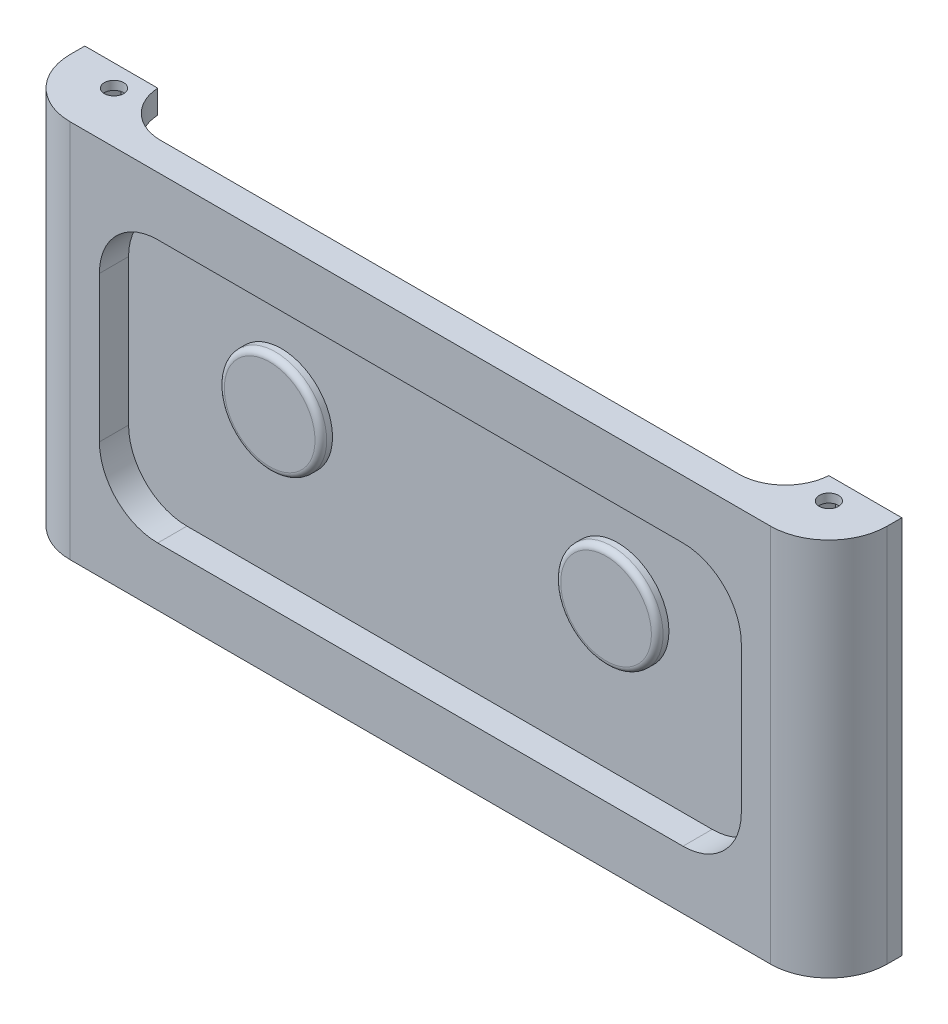
SolidWorks part; units mm, degrees
ref_plane "Front Plane" through (0, 0, 0) normal (0, 0, 1) x (1, 0, 0)
ref_plane "Top Plane" through (0, 0, 0) normal (0, 1, 0) x (1, 0, 0)
ref_plane "Right Plane" through (0, 0, 0) normal (1, 0, 0) x (0, 0, -1)
sketch "Sketch1" plane through (0, 0, 0) normal (0, 0, 1) x (1, 0, 0)
  line L1 (0, 0) -> (140, 0)
  line L2 (0, 0) -> (0, 65)
  line L3 (0, 65) -> (140, 65)
  line L4 (140, 0) -> (140, 65)
  dimension "D1" = 140
  dimension "D2" = 65
extrude "Boss-Extrude1" add sketch "Sketch1" along normal blind 12.5
sketch "Sketch4" plane through (0, 65, 0) normal (0, 1, 0) x (1, 0, 0)
  line L6 (5, 0) -> (135, 0)
  line L9 (135, 0) -> (135, -7.5)
  line L10 (5, -7.5) -> (5, 0)
  line L11 (135, -7.5) -> (5, -7.5)
  line L12 (135, 0) -> (135, -7.5)
  line L13 (5, -7.5) -> (5, 0)
  line L14 (135, -7.5) -> (5, -7.5)
  dimension "D1" = 5
extrude "Cut-Extrude3" cut sketch "Sketch4" against normal through all
sketch "Sketch2" plane through (0, 0, 12.5) normal (0, 0, 1) x (1, 0, 0)
  line L0 (70, 65) -> (70, 0) construction
  line L1 (140, 65) -> (0, 65) construction
  line L2 (0, 0) -> (140, 0) construction
  line L3 (140, 0) -> (140, 65) construction
  line L4 (15, 55) -> (125, 55)
  line L5 (15, 55) -> (15, 10)
  line L6 (15, 10) -> (125, 10)
  line L7 (125, 55) -> (125, 10)
  line L8 (15, 55) -> (125, 10) construction
  line L9 (15, 10) -> (125, 55) construction
  point P6 (70, 32.5)
  dimension "D1" = 15
  dimension "D2" = 10
extrude "Cut-Extrude1" cut sketch "Sketch2" against normal through all
fillet "Fillet1" radius 10 4 edges at (15, 10, 10) (15, 55, 10) (125, 10, 10) (125, 55, 10)
fillet "Fillet2" radius 10 2 edges at (140, 32.5, 12.5) (0, 32.5, 12.5)
sketch "Sketch5" plane through (0, 0, 0) normal (0, -1, 0) x (1, 0, 0)
  line L0 (0, 0) -> (5, 0) construction
  line L1 (5, 7.5) -> (12.5, 7.5)
  line L2 (5, 7.5) -> (5, 0)
  line L3 (5, 0) -> (12.5, 0)
  line L4 (12.5, 7.5) -> (12.5, 0)
  line L5 (135, 7.5) -> (127.5, 7.5)
  line L6 (135, 7.5) -> (135, 0)
  line L7 (135, 0) -> (127.5, 0)
  line L8 (127.5, 7.5) -> (127.5, 0)
extrude "Boss-Extrude2" add sketch "Sketch5" against normal blind 4
sketch "Sketch6" plane through (0, 4, 0) normal (0, 1, 0) x (1, 0, 0)
  line L0 (8.75, 0) -> (8.75, -7.5) construction
  line L1 (11.9254, -3.75) -> (10.3377, -1)
  line L2 (10.3377, -1) -> (7.1623, -1)
  line L3 (7.1623, -1) -> (5.5746, -3.75)
  line L4 (5.5746, -3.75) -> (7.1623, -6.5)
  line L5 (7.1623, -6.5) -> (10.3377, -6.5)
  line L6 (10.3377, -6.5) -> (11.9254, -3.75)
  line L7 (5, 0) -> (12.5, 0) construction
  line L8 (12.5, -7.5) -> (5, -7.5) construction
  line L9 (70, -12.5) -> (70, 1.5241) construction
  line L10 (130, -12.5) -> (10, -12.5) construction
  line L11 (134.4254, -3.75) -> (132.8377, -6.5)
  line L12 (132.8377, -6.5) -> (129.6623, -6.5)
  line L13 (129.6623, -6.5) -> (128.0746, -3.75)
  line L14 (128.0746, -3.75) -> (129.6623, -1)
  line L15 (129.6623, -1) -> (132.8377, -1)
  line L16 (132.8377, -1) -> (134.4254, -3.75)
  circle A0 centre (8.75, -3.75) radius 2.75 construction
  circle A1 centre (8.75, -3.75) radius 1.65
  circle A2 centre (131.25, -3.75) radius 1.65
  dimension "D1" = 3.3
  dimension "D2" = 5.5
extrude "Cut-Extrude5" cut sketch "Sketch6<2>" against normal through all contours A1 | A2 region at (8.75, 4, 3.75) region at (131.25, 4, 3.75)
sketch "Sketch6<2>" plane through (0, 4, 0) normal (0, 1, 0) x (1, 0, 0) same geometry as "Sketch6"
extrude "Cut-Extrude4" cut sketch "Sketch6" against normal blind 2.5
fillet "Fillet3" radius 8 2 edges at (127.5, 2, 7.5) (12.5, 2, 7.5)
ref_plane "Plane1" through (0, 32.5, 0) normal (0, 1, 0) x (1, 0, 0)
mirror "Mirror1" about plane through (0, 32.5, 0) normal (0, 1, 0) of "Cut-Extrude5", "Cut-Extrude4", "Boss-Extrude2", "Fillet3"
sketch "Sketch7" plane through (0, 0, 7.5) normal (0, 0, -1) x (-1, 0, 0)
  line L1 (-135, 61) -> (-5, 61)
  line L2 (-135, 61) -> (-135, 4)
  line L3 (-135, 4) -> (-5, 4)
  line L4 (-5, 61) -> (-5, 4)
extrude "Boss-Extrude3" add sketch "Sketch7" along normal blind 1 separate body
sketch "Sketch8" plane through (0, 0, 7.5) normal (0, 0, 1) x (1, 0, 0)
  line L0 (70, 55) -> (70, 24.7719) construction
  line L1 (115, 55) -> (25, 55) construction
  line L2 (25, 10) -> (115, 10) construction
  line L3 (41.1771, 35.6804) -> (98.8229, 35.6804) construction
  line L5 (70, 19.7719) -> (70, 10) construction
  circle A0 centre (41.1771, 35.6804) radius 8.769
  circle A1 centre (98.8229, 35.6804) radius 8.769
  point P11 (70, 35.6804)
extrude "Boss-Extrude4" add sketch "Sketch8" along normal blind 2 separate body contours A0 | A1 region at (41.1771, 35.6804, 7.5) region at (98.8229, 35.6804, 7.5)
sketch "Sketch9" plane through (0, 0, 6.5) normal (0, 0, -1) x (-1, 0, 0)
  line L0 (-19, 0) -> (-19, 42.7) construction
  line L1 (-20.4844, 0) -> (-119.5156, 0) construction
  line L2 (0, 0) -> (-19, 0) construction
  line L3 (-70, 65) -> (-70, 0) construction
  line L4 (-20.4844, 65) -> (-119.5156, 65) construction
  circle A0 centre (-19, 42.7) radius 8.4
  circle A1 centre (-121, 42.7) radius 8.4
  dimension "D3" = 16.8
  dimension "D1" = 19
  dimension "D2" = 42.7
extrude "Boss-Extrude6" add sketch "Sketch9" along normal blind 10 separate body
combine bodies "Combine1" operation type add bodies to combine 116 110 117
chamfer "Chamfer1" distance 3 angle 45 2 edges at (10.6, 42.7, 6.5) (112.6, 42.7, 6.5)
fillet "Fillet5" radius 1 2 edges at (10.6, 42.7, -3.5) (129.4, 42.7, -3.5)
fillet "Fillet6" radius 1 1 edges at (107.5919, 35.6804, 9.5)
fillet "Fillet7" radius 1 1 edges at (49.9461, 35.6804, 9.5)
